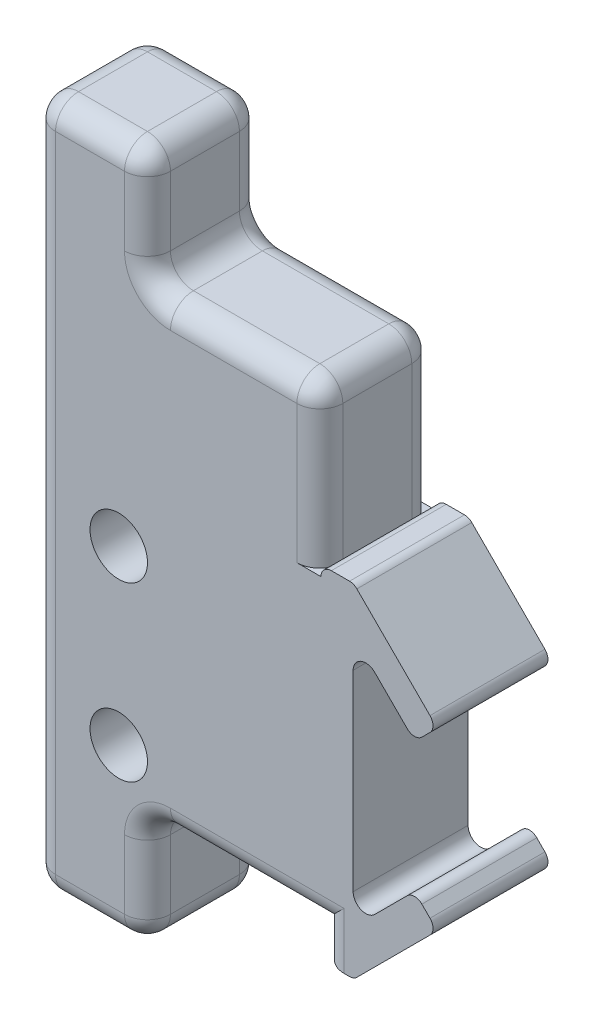
SolidWorks part; units mm, degrees
ref_plane "Plan de face" through (0, 0, 0) normal (0, 0, 1) x (1, 0, 0)
ref_plane "Plan de dessus" through (0, 0, 0) normal (0, 1, 0) x (1, 0, 0)
ref_plane "Plan de droite" through (0, 0, 0) normal (1, 0, 0) x (0, 0, -1)
sketch "Esquisse1" plane through (0, 0, 0) normal (0, 0, 1) x (1, 0, 0)
  line L0 (3.2929, 14.7071) -> (9.6569, 8.3431)
  line L1 (0, 0) -> (3, 0)
  line L2 (0, -14) -> (0, 14)
  line L3 (1, 15) -> (2.5858, 15)
  line L4 (3, -8.3431) -> (3, 8.3431)
  line L5 (10.364, 7.636) -> (3, 15)
  line L6 (9.6569, 6.9289) -> (8.9497, 6.2218)
  line L7 (3, 15) -> (2.9365, 14.9365)
  line L8 (7.5355, 6.2218) -> (4.7071, 9.0503)
  line L9 (7.5355, -6.2218) -> (4.7071, -9.0503)
  line L10 (9.6569, -6.9289) -> (8.9497, -6.2218)
  line L11 (3.2929, -14.7071) -> (9.6569, -8.3431)
  line L12 (1, -15) -> (2.5858, -15)
  line L13 (3.2222, -14.6364) -> (9.5861, -8.2724)
  line L14 (9.5861, -6.9996) -> (8.879, -6.2925)
  line L15 (7.6062, -6.2925) -> (4.7778, -9.121)
  line L16 (2.9, -8.3431) -> (2.9, 8.3431)
  line L17 (7.6062, 6.2925) -> (4.7778, 9.121)
  line L18 (9.5861, 6.9996) -> (8.879, 6.2925)
  line L19 (3.2222, 14.6364) -> (9.5861, 8.2724)
  line L20 (1, 14.9) -> (2.5858, 14.9)
  line L21 (0.1, -14) -> (0.1, 14)
  line L22 (1, -14.9) -> (2.5858, -14.9)
  line L23 (-17.5, 28) -> (-17.5, -12)
  line L24 (0, -12) -> (-25, -12)
  line L25 (0, -12) -> (0, 28)
  line L26 (0, 28) -> (-25, 28)
  line L27 (-25, -12) -> (-25, 28)
  line L28 (0, -12) -> (0.1, -12)
  line L29 (-25, 28) -> (-15, 28)
  line L30 (-25, 28) -> (-25, 38)
  line L31 (-25, 38) -> (-15, 38)
  line L32 (-15, 28) -> (-15, 38)
  line L33 (-25, -12) -> (-15, -12)
  line L34 (-25, -12) -> (-25, -22)
  line L35 (-25, -22) -> (-15, -22)
  line L36 (-15, -12) -> (-15, -22)
  line L37 (0, 14) -> (0.1, 14)
  arc A0 (3, 8.3431) -> (4.7071, 9.0503) centre (4, 8.3431) cw
  arc A1 (8.9497, 6.2218) -> (7.5355, 6.2218) centre (8.2426, 6.9289) cw
  arc A2 (9.6569, 8.3431) -> (9.6569, 6.9289) centre (8.9497, 7.636) cw
  arc A3 (3.2929, 14.7071) -> (2.5858, 15) centre (2.5858, 14) ccw
  arc A4 (1, 15) -> (0, 14) centre (1, 14) ccw
  arc A5 (3, -8.3431) -> (4.7071, -9.0503) centre (4, -8.3431) ccw
  arc A6 (8.9497, -6.2218) -> (7.5355, -6.2218) centre (8.2426, -6.9289) ccw
  arc A7 (9.6569, -8.3431) -> (9.6569, -6.9289) centre (8.9497, -7.636) ccw
  arc A8 (3.2929, -14.7071) -> (2.5858, -15) centre (2.5858, -14) cw
  arc A9 (1, -15) -> (0, -14) centre (1, -14) cw
  arc A10 (9.5861, -8.2724) -> (9.5861, -6.9996) centre (8.9497, -7.636) ccw
  arc A11 (8.879, -6.2925) -> (7.6062, -6.2925) centre (8.2426, -6.9289) ccw
  arc A12 (2.9, -8.3431) -> (4.7778, -9.121) centre (4, -8.3431) ccw
  arc A13 (2.9, 8.3431) -> (4.7778, 9.121) centre (4, 8.3431) cw
  arc A14 (8.879, 6.2925) -> (7.6062, 6.2925) centre (8.2426, 6.9289) cw
  arc A15 (9.5861, 8.2724) -> (9.5861, 6.9996) centre (8.9497, 7.636) cw
  arc A16 (3.2222, 14.6364) -> (2.5858, 14.9) centre (2.5858, 14) ccw
  arc A17 (1, 14.9) -> (0.1, 14) centre (1, 14) ccw
  arc A18 (1, -14.9) -> (0.1, -14) centre (1, -14) cw
  arc A19 (3.2222, -14.6364) -> (2.5858, -14.9) centre (2.5858, -14) cw
  circle A20 centre (-17.5, 7.5) radius 2.5
  circle A21 centre (-17.5, -7.5) radius 2.5
  point P13 (8.2426, 5.5147)
  point P22 (0, 15)
  dimension "D2" = 1
  dimension "D3" = 1
  dimension "D6" = 1
  dimension "D7" = 1
  dimension "D8" = 1
  dimension "D17" = 5
  dimension "D18" = 5
  dimension "D1" = 15
  dimension "D4" = 3
  dimension "D5" = 45
  dimension "D9" = 9
  dimension "D10" = 4
  dimension "D11" = 3
  dimension "D13" = 25
  dimension "D14" = 3
  dimension "D15" = 13
  dimension "D16" = 17.5
  dimension "D19" = 7.5
  dimension "D20" = 7.5
  dimension "D21" = 10
  dimension "D22" = 10
  dimension "D23" = 10
  dimension "D24" = 10
  dimension "D12" = 0.1
extrude "Boss.-Extru.1" add sketch "Esquisse1" along normal blind 10 contours A19 L13 A10 L14 A11 L15 A12 L16 L1 L21 A18 L22 | L20 A17 L21 L1 L16 A13 L17 A14 L18 A15 L19 A16 | L2 L28 L21 L1 | A21 L23 A20 L26 L27 L24 | L36 L24 L34 L35 | L26 L32 L31 L30 | L37 L2 L1 L21 | A21 L23 L24 L2 L25 L26 A20
fillet "Congé1" radius 2 25 edges at (-15, -12, 5) (-25, -22, 5) (-15, -22, 5) (0, 28, 5) (-15, 28, 5) (-15, 38, 5) (-25, 38, 5) (-15, 33, 0) (-15, 33, 10) (-7.45, -12, 0) (-7.45, -12, 10) (-20, 38, 0) (-20, 38, 10) (-7.5, 28, 0) (-7.5, 28, 10) (0, 21, 0) (0, 21, 10) (-15, -17, 0) (-15, -17, 10) (-20, -22, 0) (-20, -22, 10) (-25, 8, 0) (-25, 8, 10) (0.1, -13, 0) (0.1, -13, 10)
